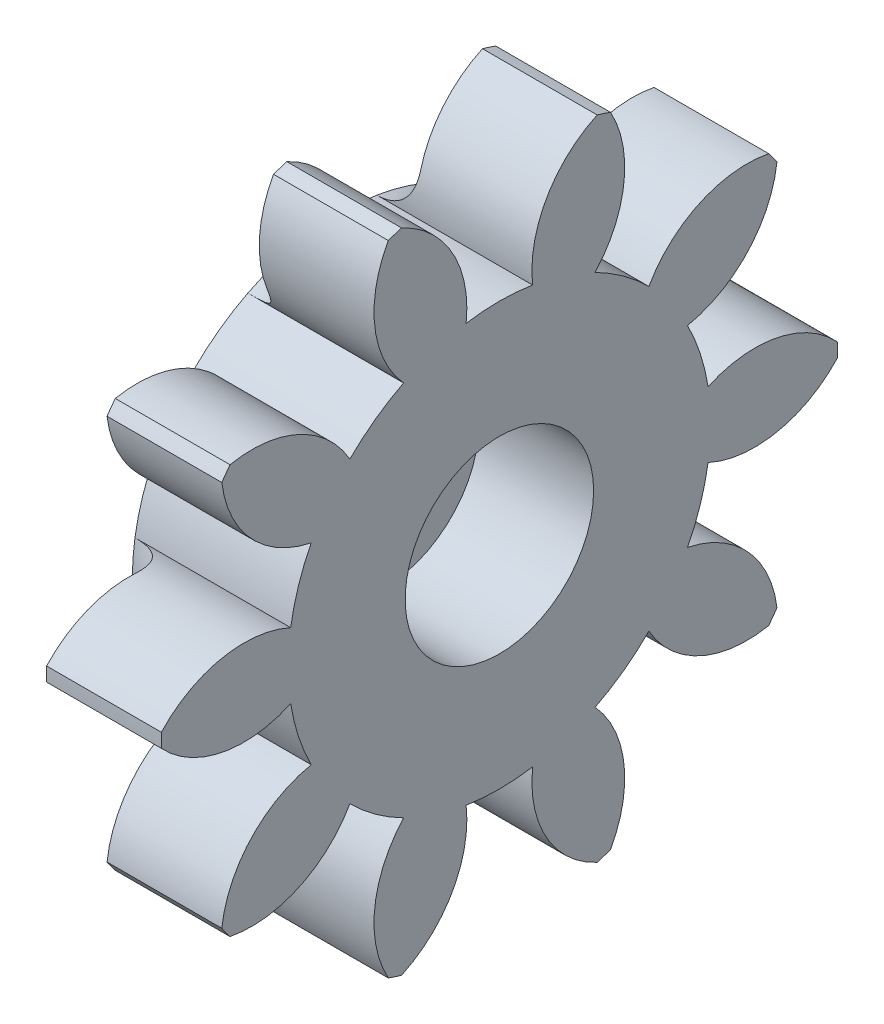
SolidWorks part; units mm, degrees
ref_plane "Plane1" through (0, 0, 0) normal (0, 0, 1) x (1, 0, 0)
ref_plane "Plane2" through (0, 0, 0) normal (0, 1, 0) x (1, 0, 0)
ref_plane "Plane3" through (0, 0, 0) normal (1, 0, 0) x (0, 0, -1)
sketch "HoldingSke" plane through (0, 0, 0) normal (0, 1, 0) x (1, 0, 0)
  line L0 (0, 0) -> (0.7162, -0.1263)
  line L1 (-15, 0) -> (100, 0) construction
  line L2 (0, 0) -> (-2.1039, 2.3779)
  line L3 (0, 0) -> (-11.863, 4.5341)
  line L4 (0, 0) -> (8.5048, 1.4996)
  line L5 (0, 0) -> (-46.8476, -17.4728)
  line L6 (0, 0) -> (-1.6579, -1.1186)
  line L7 (-2.1039, 2.3779) -> (8.6586, 51.2059)
  line L8 (-76.2, 54.61) -> (-75.3, 54.61)
  line L9 (-71.009, 38.7566) -> (-53.1078, 45.2721)
  line L10 (-76.2, 71.12) -> (104.1128, 71.12)
  line L11 (0, 0) -> (-2, 0)
  line L12 (-76.2, 101.6) -> (-76.151, 101.6)
  line L13 (24.9733, 27.94) -> (52.9518, 28.4284)
  line L14 (24.9733, 27.94) -> (24.9743, 27.94)
  line L15 (24.9733, 27.94) -> (100.4006, 29.5858)
  line L16 (-63.627, -1.375) -> (-12.827, -1.375)
  circle A0 centre (0, 0) radius 2.5
  circle A1 centre (0, 0) radius 5.1552
  circle A2 centre (0, 0) radius 37.5
  circle A3 centre (0, 0) radius 2.5
  dimension "Num_teeth" = 10
  dimension "Pitch_radius" = 180.3128
  dimension "Width" = 2
  dimension "Thickness" = 2
sketch "BasProSke" plane through (0, 0, 0) normal (0, 1, 0) x (1, 0, 0)
  line L0 (-10, 0) -> (60, 0) construction
  line L1 (0, 0) -> (0, 8.25)
  line L2 (0, 0) -> (2, 0)
  line L3 (2, 0) -> (2, 8.25)
  line L4 (2, 8.25) -> (0, 8.25)
  dimension "Thickness" = 2
  dimension "Diameter" = 16.5
revolve "Base-Revolve" add sketch "BasProSke" angle 360 about L0
sketch "TooCutSke" plane through (0, 0, 0) normal (1, 0, 0) x (0, 0, -1)
  line L1 (0, 0) -> (0, 107) construction
  line L2 (0, 0) -> (-1.1611, 6.7762) construction
  line L3 (0, 0) -> (-4.2047, 12.9408) construction
  line L4 (-1.1611, 6.7762) -> (-2.1024, 6.4704) construction
  arc A0 (0.8108, 5.0911) -> (-0.8108, 5.0911) centre (0, 0) ccw
  arc A1 (2.4218, 7.9131) -> (-2.4218, 7.9131) centre (0, 0) ccw
  circle A2 centre (0, 0) radius 6.875 construction
  circle A3 centre (0, 0) radius 6.4604 construction
  arc A4 (-0.8108, 5.0911) -> (-2.4218, 7.9131) centre (-3.5431, 5.4021) ccw
  arc A5 (2.4218, 7.9131) -> (0.8108, 5.0911) centre (3.5431, 5.4021) ccw
extrude "ToothCut" cut sketch "TooCutSke" along normal through all
fillet "Breaks" [suppressed] radius 0.0275 tangent propagation no
fillet "RootFillets" [suppressed] radius 0.3447
pattern_circular "TeethCuts" count 10 every 36 about axis through (-10, 0, 0) along (1, 0, 0) of "ToothCut", "RootFillets", "Breaks"
sketch "HubNeaOneSke" plane through (0, 0, 0) normal (-1, 0, 0) x (0, 0, 1)
  circle A0 centre (0, 0) radius 5.1552
  dimension "Diameter" = 10.3105
extrude "HubNearOne" [suppressed] add sketch "HubNeaOneSke" along normal blind 48.0001
sketch "HubNeaBotSke" plane through (0, 0, 0) normal (-1, 0, 0) x (0, 0, 1)
  circle A0 centre (0, 0) radius 5.1552
  dimension "Diameter" = 10.3105
extrude "HubNearBoth" [suppressed] add sketch "HubNeaBotSke" along normal blind 24
ref_plane "FarPln" through (2, 0, 0) normal (1, 0, 0) x (0, 0, -1)
sketch "HubFarSke" plane through (2, 0, 0) normal (1, 0, 0) x (0, 0, -1)
  circle A0 centre (0, 0) radius 5.1552
  dimension "Diameter" = 10.3105
extrude "HubFar" [suppressed] add sketch "HubFarSke" along normal blind 24
sketch "BorSke" plane through (0, 0, 0) normal (1, 0, 0) x (0, 0, -1)
  circle A0 centre (0, 0) radius 2.5
  dimension "Diameter" = 5
extrude "Bore" cut sketch "BorSke" along normal mid plane 100.0001
sketch "KeySke" plane through (0, 0, 0) normal (1, 0, 0) x (0, 0, -1)
  line L0 (-1, 0) -> (-1, 3.4)
  line L1 (-1, 3.4) -> (1, 3.4)
  line L2 (1, 3.4) -> (1, 0)
  line L3 (0, 0) -> (0, 34) construction
  line L4 (-1, 0) -> (1, 0)
  dimension "Width" = 2
extrude "Keyway" [suppressed] cut sketch "KeySke" along normal mid plane 100.0001
pattern_circular "Keyway2" [suppressed] count 2 every 90 about axis through (-10, 0, 0) along (1, 0, 0)
sketch "Sketch1" plane through (0, 0, 0) normal (-1, 0, 0) x (0, 0, 1)
  circle A0 centre (0, 0) radius 2.5 construction
  circle A1 centre (0, 0) radius 2.5
  arc A40 (-5.0925, 0.8021) -> (-8.2482, 0.1704) centre (-6.2326, -1.7004) ccw
  arc A41 (-8.2482, 0.1704) -> (-8.2482, -0.1704) centre (0, 0) ccw
  arc A42 (-8.2482, -0.1704) -> (-5.0925, -0.8021) centre (-6.2326, 1.7004) ccw
  arc A43 (-5.0925, -0.8021) -> (-4.5914, -2.3443) centre (0, 0) ccw
  arc A44 (-4.5914, -2.3443) -> (-6.7731, -4.7104) centre (-4.0428, -5.0391) ccw
  arc A45 (-6.7731, -4.7104) -> (-6.5728, -4.986) centre (0, 0) ccw
  arc A46 (-6.5728, -4.986) -> (-3.6484, -3.6422) centre (-6.0417, -2.2878) ccw
  arc A47 (-3.6484, -3.6422) -> (-2.3365, -4.5953) centre (0, 0) ccw
  arc A48 (-2.3365, -4.5953) -> (-2.7109, -7.7919) centre (-0.3088, -6.453) ccw
  arc A49 (-2.7109, -7.7919) -> (-2.3868, -7.8972) centre (0, 0) ccw
  arc A50 (-2.3868, -7.8972) -> (-0.8108, -5.0911) centre (-3.5431, -5.4021) ccw
  arc A51 (-0.8108, -5.0911) -> (0.8108, -5.0911) centre (0, 0) ccw
  arc A52 (0.8108, -5.0911) -> (2.3868, -7.8972) centre (3.5431, -5.4021) ccw
  arc A53 (2.3868, -7.8972) -> (2.7109, -7.7919) centre (0, 0) ccw
  arc A54 (2.7109, -7.7919) -> (2.3365, -4.5953) centre (0.3088, -6.453) ccw
  arc A55 (2.3365, -4.5953) -> (3.6484, -3.6422) centre (0, 0) ccw
  arc A56 (3.6484, -3.6422) -> (6.5728, -4.986) centre (6.0417, -2.2878) ccw
  arc A57 (6.5728, -4.986) -> (6.7731, -4.7104) centre (0, 0) ccw
  arc A58 (6.7731, -4.7104) -> (4.5914, -2.3443) centre (4.0428, -5.0391) ccw
  arc A59 (4.5914, -2.3443) -> (5.0925, -0.8021) centre (0, 0) ccw
  arc A60 (5.0925, -0.8021) -> (8.2482, -0.1704) centre (6.2326, 1.7004) ccw
  arc A61 (8.2482, -0.1704) -> (8.2482, 0.1704) centre (0, 0) ccw
  arc A62 (8.2482, 0.1704) -> (5.0925, 0.8021) centre (6.2326, -1.7004) ccw
  arc A63 (5.0925, 0.8021) -> (4.5914, 2.3443) centre (0, 0) ccw
  arc A64 (4.5914, 2.3443) -> (6.7731, 4.7104) centre (4.0428, 5.0391) ccw
  arc A65 (6.7731, 4.7104) -> (6.5728, 4.986) centre (0, 0) ccw
  arc A66 (6.5728, 4.986) -> (3.6484, 3.6422) centre (6.0417, 2.2878) ccw
  arc A67 (3.6484, 3.6422) -> (2.3365, 4.5953) centre (0, 0) ccw
  arc A68 (2.3365, 4.5953) -> (2.7109, 7.7919) centre (0.3088, 6.453) ccw
  arc A69 (2.7109, 7.7919) -> (2.3868, 7.8972) centre (0, 0) ccw
  arc A70 (2.3868, 7.8972) -> (0.8108, 5.0911) centre (3.5431, 5.4021) ccw
  arc A71 (0.8108, 5.0911) -> (-0.8108, 5.0911) centre (0, 0) ccw
  arc A72 (-0.8108, 5.0911) -> (-2.3868, 7.8972) centre (-3.5431, 5.4021) ccw
  arc A73 (-2.3868, 7.8972) -> (-2.7109, 7.7919) centre (0, 0) ccw
  arc A74 (-2.7109, 7.7919) -> (-2.3365, 4.5953) centre (-0.3088, 6.453) ccw
  arc A75 (-2.3365, 4.5953) -> (-3.6484, 3.6422) centre (0, 0) ccw
  arc A76 (-3.6484, 3.6422) -> (-6.5728, 4.986) centre (-6.0417, 2.2878) ccw
  arc A77 (-6.5728, 4.986) -> (-6.7731, 4.7104) centre (0, 0) ccw
  arc A78 (-6.7731, 4.7104) -> (-4.5914, 2.3443) centre (-4.0428, 5.0391) ccw
  arc A79 (-4.5914, 2.3443) -> (-5.0925, 0.8021) centre (0, 0) ccw
  arc A80 (-5.0925, 0.8021) -> (-8.2482, 0.1704) centre (-6.2326, -1.7004) ccw
  arc A81 (-8.2482, 0.1704) -> (-8.2482, -0.1704) centre (0, 0) ccw
  arc A82 (-8.2482, -0.1704) -> (-5.0925, -0.8021) centre (-6.2326, 1.7004) ccw
  arc A83 (-5.0925, -0.8021) -> (-4.5914, -2.3443) centre (0, 0) ccw
  arc A84 (-4.5914, -2.3443) -> (-6.7731, -4.7104) centre (-4.0428, -5.0391) ccw
  arc A85 (-6.7731, -4.7104) -> (-6.5728, -4.986) centre (0, 0) ccw
  arc A86 (-6.5728, -4.986) -> (-3.6484, -3.6422) centre (-6.0417, -2.2878) ccw
  arc A87 (-3.6484, -3.6422) -> (-2.3365, -4.5953) centre (0, 0) ccw
  arc A88 (-2.3365, -4.5953) -> (-2.7109, -7.7919) centre (-0.3088, -6.453) ccw
  arc A89 (-2.7109, -7.7919) -> (-2.3868, -7.8972) centre (0, 0) ccw
  arc A90 (-2.3868, -7.8972) -> (-0.8108, -5.0911) centre (-3.5431, -5.4021) ccw
  arc A91 (-0.8108, -5.0911) -> (0.8108, -5.0911) centre (0, 0) ccw
  arc A92 (0.8108, -5.0911) -> (2.3868, -7.8972) centre (3.5431, -5.4021) ccw
  arc A93 (2.3868, -7.8972) -> (2.7109, -7.7919) centre (0, 0) ccw
  arc A94 (2.7109, -7.7919) -> (2.3365, -4.5953) centre (0.3088, -6.453) ccw
  arc A95 (2.3365, -4.5953) -> (3.6484, -3.6422) centre (0, 0) ccw
  arc A96 (3.6484, -3.6422) -> (6.5728, -4.986) centre (6.0417, -2.2878) ccw
  arc A97 (6.5728, -4.986) -> (6.7731, -4.7104) centre (0, 0) ccw
  arc A98 (6.7731, -4.7104) -> (4.5914, -2.3443) centre (4.0428, -5.0391) ccw
  arc A99 (4.5914, -2.3443) -> (5.0925, -0.8021) centre (0, 0) ccw
  arc A100 (5.0925, -0.8021) -> (8.2482, -0.1704) centre (6.2326, 1.7004) ccw
  arc A101 (8.2482, -0.1704) -> (8.2482, 0.1704) centre (0, 0) ccw
  arc A102 (8.2482, 0.1704) -> (5.0925, 0.8021) centre (6.2326, -1.7004) ccw
  arc A103 (5.0925, 0.8021) -> (4.5914, 2.3443) centre (0, 0) ccw
  arc A104 (4.5914, 2.3443) -> (6.7731, 4.7104) centre (4.0428, 5.0391) ccw
  arc A105 (6.7731, 4.7104) -> (6.5728, 4.986) centre (0, 0) ccw
  arc A106 (6.5728, 4.986) -> (3.6484, 3.6422) centre (6.0417, 2.2878) ccw
  arc A107 (3.6484, 3.6422) -> (2.3365, 4.5953) centre (0, 0) ccw
  arc A108 (2.3365, 4.5953) -> (2.7109, 7.7919) centre (0.3088, 6.453) ccw
  arc A109 (2.7109, 7.7919) -> (2.3868, 7.8972) centre (0, 0) ccw
  arc A110 (2.3868, 7.8972) -> (0.8108, 5.0911) centre (3.5431, 5.4021) ccw
  arc A111 (0.8108, 5.0911) -> (-0.8108, 5.0911) centre (0, 0) ccw
  arc A112 (-0.8108, 5.0911) -> (-2.3868, 7.8972) centre (-3.5431, 5.4021) ccw
  arc A113 (-2.3868, 7.8972) -> (-2.7109, 7.7919) centre (0, 0) ccw
  arc A114 (-2.7109, 7.7919) -> (-2.3365, 4.5953) centre (-0.3088, 6.453) ccw
  arc A115 (-2.3365, 4.5953) -> (-3.6484, 3.6422) centre (0, 0) ccw
  arc A116 (-3.6484, 3.6422) -> (-6.5728, 4.986) centre (-6.0417, 2.2878) ccw
  arc A117 (-6.5728, 4.986) -> (-6.7731, 4.7104) centre (0, 0) ccw
  arc A118 (-6.7731, 4.7104) -> (-4.5914, 2.3443) centre (-4.0428, 5.0391) ccw
  arc A119 (-4.5914, 2.3443) -> (-5.0925, 0.8021) centre (0, 0) ccw
  dimension "D1" = 0
extrude "Boss-Extrude1" add sketch "Sketch1" along normal up to surface (0.8 mm away)
sketch "Sketch2" plane through (2, 0, 0) normal (1, 0, 0) x (0, 0, -1)
  circle A0 centre (0, 0) radius 2.55
  circle A1 centre (0, 0) radius 2.3
  dimension "D1" = 5.1
  dimension "D2" = 4.6
extrude "Boss-Extrude2" add sketch "Sketch2" against normal up to surface (2.8 mm away) up to face at (-0.8, 0, 2.5)
sketch "Sketch3" plane through (-0.8, 0, 0) normal (-1, 0, 0) x (0, 0, 1)
  circle A0 centre (0, 0) radius 5.1552
  circle A1 centre (0, 0) radius 1
  arc A3 (-0.8108, -5.0911) -> (0.8108, -5.0911) centre (0, 0) ccw construction
  dimension "D1" = 2
  dimension "D2" = 0
extrude "Boss-Extrude3" add sketch "Sketch3" along normal blind 1
fillet "Fillet1" radius 1 5 edges at (-0.8, 4.9029, -1.5931) (-0.8, 0, -5.1552) (-0.8, -4.9029, -1.5931) (-0.8, -3.0302, 4.1707) (-0.8, 3.0302, 4.1707)
equation "' \"Module@HoldingSke\" = 6.35"
equation "' \"Num_teeth@HoldingSke\" = 12"
equation "' \"Ap@HoldingSke\" =  20"
equation "' \"Ap@HoldingSke\" = 20"
equation "' \"Width@HoldingSke\" = 0.5 * 25.4"
equation "' \"Hub_dia@HoldingSke\"= 1 * 25.4"
equation "' \"Hub_dia@HoldingSke\" = 1 * 25.4"
equation "' \"Overall_len@HoldingSke\" = 1.0 * 25.4"
equation "' \"Bore@HoldingSke\" = 0.75 * 25.4"
equation "' \"T_dim@HoldingSke\" = 0.1 * 25.4"
equation "' \"Width@KeySke\" = 0.25 * 25.4"
equation "' \"Show_teeth@HoldingSke\" = 13"
equation "' \"Backlash@HoldingSke\" = 0.009 * 25.4"
equation "' \"Addendum_fac@HoldingSke\" = 1.0"
equation "' \"Dedendum_fac@HoldingSke\" = 1.25"
equation "' \"Dedendum_add@HoldingSke\" = 0.00005 * 25.4"
equation "' \"Clearance_fac@HoldingSke\" = 0.25"
equation "\"Pitch@HoldingSke\" = 1 / \"Module@HoldingSke\""
equation "\"Overcut_dia@TooCutSke\" = (\"Num_teeth@HoldingSke\" + 2 * \"Addendum_fac@HoldingSke\") / \"Pitch@HoldingSke\" + 0.002 * 25.4"
equation "\"Pitch_dia@TooCutSke\" = \"Num_teeth@HoldingSke\" / \"Pitch@HoldingSke\""
equation "\"Base_dia@TooCutSke\" = \"Num_teeth@HoldingSke\" / \"Pitch@HoldingSke\" * cos((\"Ap@HoldingSke\"  * 3.14159265 / 180))"
equation "\"Root_dia@TooCutSke\" = (\"Num_teeth@HoldingSke\" + 2) / \"Pitch@HoldingSke\" - 2 * (\"Addendum_fac@HoldingSke\" + \"Dedendum_fac@HoldingSke\") / \"Pitch@HoldingSke\" - \"Dedendum_add@HoldingSke\" * 2"
equation "\"Half_ang@TooCutSke\" = 180 / \"Num_teeth@HoldingSke\""
equation "\"Half_CT@TooCutSke\" = \"Num_teeth@HoldingSke\" / \"Pitch@HoldingSke\" * sin((3.14159265 / 2 / \"Num_teeth@HoldingSke\")) / 2 - 7 * \"Backlash@HoldingSke\" / 4"
equation "\"Flank_rad@TooCutSke\" = \"Num_teeth@HoldingSke\" / \"Pitch@HoldingSke\" / 5"
equation "\"Radius@RootFillets\" = \"Clearance_fac@HoldingSke\" / \"Pitch@HoldingSke\" + \"Dedendum_add@HoldingSke\""
equation "\"Break_rad@Breaks\" = 0.02 / \"Pitch@HoldingSke\""
equation "\"Thickness@HoldingSke\" = \"Width@HoldingSke\""
equation "\"OAL@HoldingSke\" = \"Thickness@HoldingSke\""
equation "\"MHD@HoldingSke\" = (\"Num_teeth@HoldingSke\" + 2) / \"Pitch@HoldingSke\" - 2 * (\"Addendum_fac@HoldingSke\" + \"Dedendum_fac@HoldingSke\")  / \"Pitch@HoldingSke\" - \"Dedendum_add@HoldingSke\" * 2"
equation "\"MBD@HoldingSke\" = (\"Num_teeth@HoldingSke\" + 2) / \"Pitch@HoldingSke\" - 2 * (\"Addendum_fac@HoldingSke\" + \"Dedendum_fac@HoldingSke\")  / \"Pitch@HoldingSke\" - \"Dedendum_add@HoldingSke\" * 2 - 0.002 * 25.4"
equation "\"MHD@HoldingSke\" = ((sgn( \"MHD@HoldingSke\" - \"Hub_dia@HoldingSke\" )-1)*( \"MHD@HoldingSke\" - \"Hub_dia@HoldingSke\" ))/-2+ \"Hub_dia@HoldingSke\""
equation "\"MBD@HoldingSke\" = ((sgn( \"MBD@HoldingSke\" - \"Bore@HoldingSke\" )-1)*( \"MBD@HoldingSke\" - \"Bore@HoldingSke\" ))/-2+ \"Bore@HoldingSke\""
equation "\"OAL@HoldingSke\" = ((sgn( \"OAL@HoldingSke\" - \"Overall_len@HoldingSke\" )+1)*( \"OAL@HoldingSke\" - \"Overall_len@HoldingSke\" ))/2 + \"Overall_len@HoldingSke\" + 0.000002 * 25.4"
equation "\"Num_teeth@TeethCuts\" = int( \"Show_teeth@HoldingSke\" ) + 1"
equation "\"Num_teeth@TeethCuts\" = ((sgn( \"Num_teeth@TeethCuts\" - \"Num_teeth@HoldingSke\" )-1)*( \"Num_teeth@TeethCuts\" - \"Num_teeth@HoldingSke\" ))/-2+ \"Num_teeth@HoldingSke\""
equation "\"Num_teeth@TeethCuts\" = ((sgn( \"Num_teeth@TeethCuts\" - 2.0)+1)*( \"Num_teeth@TeethCuts\" - 2.0))/2 +2.0"
equation "\"Angle@TeethCuts\" = 360.0 / \"Num_teeth@HoldingSke\""
equation "\"Diameter@BasProSke\" = (\"Num_teeth@HoldingSke\" + 2 * \"Addendum_fac@HoldingSke\") / \"Pitch@HoldingSke\""
equation "\"Thickness@BasProSke\"  = \"Thickness@HoldingSke\""
equation "' \"Fillet_rad@BasProSke\" =  \"Thickness@HoldingSke\" * 0.05"
equation "' \"Fillet_rad@BasProSke\" = \"Thickness@HoldingSke\" * 0.05"
equation "\"MHD@HoldingSke\" = ((sgn( \"MHD@HoldingSke\" - \"Root_dia@TooCutSke\" )-1)*( \"MHD@HoldingSke\" - \"Root_dia@TooCutSke\" ))/-2+ \"Root_dia@TooCutSke\""
equation "\"Diameter@HubNeaOneSke\" = \"MHD@HoldingSke\""
equation "\"Length@HubNearOne\" = \"OAL@HoldingSke\" - \"Thickness@BasProSke\""
equation "\"Diameter@HubNeaBotSke\" = \"MHD@HoldingSke\""
equation "\"Length@HubNearBoth\" = ( \"OAL@HoldingSke\" - \"Thickness@BasProSke\" ) / 2.0"
equation "\"Thickness@FarPln\" = \"Thickness@BasProSke\""
equation "\"Diameter@HubFarSke\" = \"MHD@HoldingSke\""
equation "\"Length@HubFar\" = ( \"OAL@HoldingSke\" - \"Thickness@BasProSke\" ) / 2.0"
equation "\"Diameter@BorSke\" = \"MBD@HoldingSke\""
equation "\"D1@Bore\" = \"OAL@HoldingSke\" * 2.0"
equation "\"D1@Keyway\" = \"OAL@HoldingSke\" * 2.0"
equation "\"Offset@KeySke\" = \"T_dim@HoldingSke\" + \"MBD@HoldingSke\" / 2.0"
